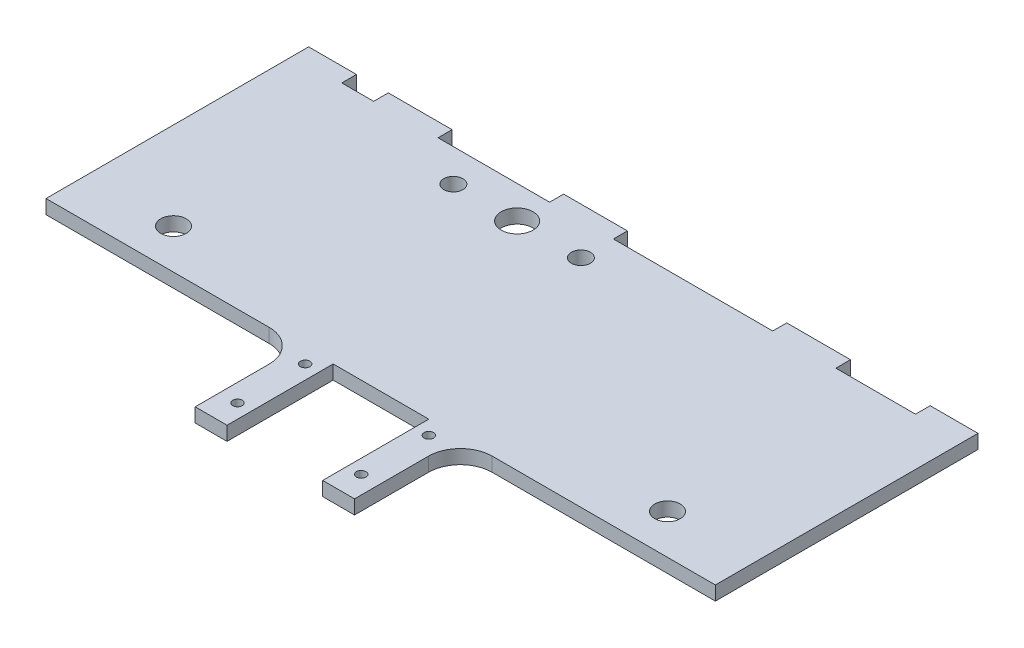
SolidWorks part; units mm, degrees
ref_plane "Front Plane" through (0, 0, 0) normal (0, 0, 1) x (1, 0, 0)
ref_plane "Top Plane" through (0, 0, 0) normal (0, 1, 0) x (1, 0, 0)
ref_plane "Right Plane" through (0, 0, 0) normal (1, 0, 0) x (0, 0, -1)
sketch "Sketch1" plane through (0, 0, 0) normal (0, 1, 0) x (1, 0, 0)
  line L0 (12.7, 98.806) -> (279.4, 98.806) construction
  line L3 (12.7, 104.648) -> (31.75, 104.648)
  line L5 (31.75, 104.648) -> (31.75, 98.806)
  line L6 (31.75, 98.806) -> (44.45, 98.806)
  line L7 (12.7, 0) -> (279.4, 0) construction
  line L8 (44.45, 98.806) -> (44.45, 104.648)
  line L10 (114.3, -42.164) -> (127, -42.164)
  line L12 (146.05, 0.1228) -> (165.1, 0.1228)
  line L13 (165.1, 0.1228) -> (165.1, -42.164)
  line L14 (146.05, 0.1228) -> (127, 0.1228)
  line L15 (127, 0.1228) -> (127, -42.164)
  line L16 (165.1, -42.164) -> (177.8, -42.164)
  line L17 (12.7, 0) -> (101.6, 0)
  line L18 (114.3, -12.7) -> (114.3, -42.164)
  line L19 (279.4, 0) -> (190.5, 0)
  line L20 (177.8, -12.7) -> (177.8, -42.164)
  line L27 (114.3, 104.648) -> (139.7, 104.648)
  line L28 (203.2, 104.648) -> (228.6, 104.648)
  line L29 (69.85, 104.648) -> (69.85, 99.06)
  line L30 (69.85, 99.06) -> (114.3, 99.06)
  line L31 (114.3, 99.06) -> (114.3, 104.648)
  line L32 (139.7, 104.648) -> (139.7, 99.06)
  line L33 (139.7, 99.06) -> (203.2, 99.06)
  line L34 (203.2, 99.06) -> (203.2, 104.648)
  line L35 (228.6, 104.648) -> (228.6, 98.806)
  line L36 (228.6, 98.806) -> (260.35, 98.806)
  line L37 (260.35, 98.806) -> (260.35, 104.648)
  line L38 (44.45, 104.648) -> (69.85, 104.648)
  line L39 (260.35, 104.648) -> (279.4, 104.648)
  line L40 (279.4, 104.648) -> (279.4, 0)
  line L41 (12.7, 104.648) -> (12.7, 0)
  arc A0 (190.5, 0) -> (177.8, -12.7) centre (190.5, -12.7) ccw
  arc A1 (114.3, -12.7) -> (101.6, 0) centre (101.6, -12.7) ccw
  point P0 (0, 0)
  point P10 (0, -41.181)
  point P27 (95.25, 0)
  dimension "D6" = 12.7
  dimension "D2" = 19.05
  dimension "D3" = 5.842
  dimension "D4" = 98.806
  dimension "D5" = 19.05
  dimension "D7" = 12.7
  dimension "D8" = 63.5
  dimension "D9" = 19.05
  dimension "D10" = 25.4
  dimension "D11" = 5.588
  dimension "D12" = 25.4
  dimension "D13" = 29.464
  dimension "D14" = 42.2868
  dimension "D15" = 12.7
  dimension "D16" = 44.45
  dimension "D17" = 25.4
  dimension "D18" = 31.75
extrude "Boss-Extrude1" add sketch "Sketch1" along normal blind 5.588
sketch "Sketch5" plane through (0, 5.588, 0) normal (0, 1, 0) x (1, 0, 0)
  line L1 (190.5, 0) -> (279.4, 0) construction
  line L3 (12.7, 0) -> (101.6, 0) construction
  line L4 (127, -42.164) -> (127, 0.1228) construction
  line L6 (165.1, 0.1228) -> (165.1, -42.164) construction
  circle A0 centre (244.475, 15.8708) radius 5.08
  circle A1 centre (47.625, 15.8708) radius 5.08
  dimension "D1" = 10.16
  dimension "D2" = 10.16
  dimension "D3" = 79.375
  dimension "D4" = 15.8708
  dimension "D5" = 79.375
  dimension "D6" = 15.8708
extrude "Cut-Extrude1" cut sketch "Sketch5" against normal up to next
sketch "Sketch6" plane through (0, 0, 0) normal (0, -1, 0) x (1, 0, 0)
  line L0 (12.7, -104.648) -> (12.7, 0) construction
  line L1 (44.45, -98.806) -> (31.75, -98.806) construction
  circle A0 centre (114.3, -86.106) radius 6.35
  dimension "D1" = 12.7
  dimension "D2" = 101.6
  dimension "D3" = 12.7
extrude "Cut-Extrude2" cut sketch "Sketch6" against normal up to next
sketch "Sketch7" plane through (0, 5.588, 0) normal (0, 1, 0) x (1, 0, 0)
  circle A0 centre (139.7, 86.106) radius 3.81
  circle A1 centre (114.3, 86.106) radius 6.35 construction
  circle A2 centre (88.9, 86.106) radius 3.81
  dimension "D1" = 7.62
  dimension "D4" = 7.62
  dimension "D5" = 0
  dimension "D2" = 25.4
  dimension "D3" = 25.4
extrude "Cut-Extrude3" cut sketch "Sketch7" against normal up to next
sketch "Sketch10" plane through (0, 5.588, 0) normal (0, 1, 0) x (1, 0, 0)
  point P0 (170.688, -5.4568)
  point P1 (170.688, -32.3976)
  point P3 (121.412, -5.4568)
  point P5 (121.412, -32.3976)
hole_wizard "#6 Clearance Hole1" positions "Sketch11" profile "Sketch12" hole size "#6" standard "ANSI Inch" end condition through all
sketch "Sketch11" plane through (0, 5.588, 0) normal (0, 1, 0) x (1, 0, 0)
  point P0 (121.412, -5.4568)
  point P3 (121.412, -32.3976)
  point P6 (170.688, -32.3976)
  point P9 (170.688, -5.4568)
sketch "Sketch12" plane through (121.412, 5.588, 5.4568) normal (1, 0, 0) x (0, 0, 1)
  line L0 (0, 0) -> (0, 5.588)
  line L1 (0, 5.588) -> (1.8986, 5.588)
  line L2 (1.8986, 5.588) -> (1.8986, 0)
  line L5 (1.8986, 0) -> (0, 0)
  line L11 (0, -6.35) -> (0, 107.95) construction
  dimension "Thru Hole Dia." = 3.7973
  dimension "Thru Hole Depth" = 5.588
